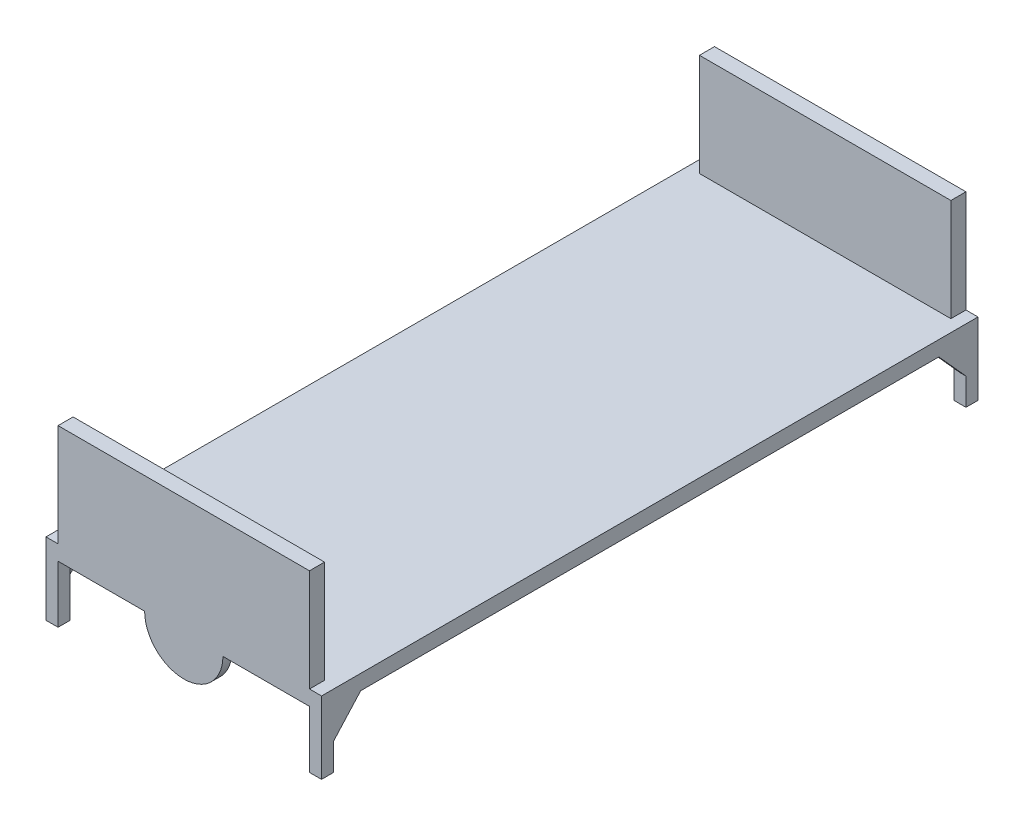
SolidWorks part; units mm, degrees
note: The reader was unsure of these and kept them because the rebuilt part matched: shared geometry of "Sketch1<3>", "Sketch1<4>".
ref_plane "Front Plane" through (0, 0, 0) normal (0, 0, 1) x (1, 0, 0)
ref_plane "Top Plane" through (0, 0, 0) normal (0, 1, 0) x (1, 0, 0)
ref_plane "Right Plane" through (0, 0, 0) normal (1, 0, 0) x (0, 0, -1)
sketch "Sketch1" plane through (0, 0, 0) normal (0, 1, 0) x (1, 0, 0)
  line L0 (-417.5, 40) -> (-457.5, 40)
  line L1 (457.5, 0) -> (-457.5, 0)
  line L2 (457.5, 0) -> (457.5, 2180)
  line L3 (457.5, 2180) -> (-457.5, 2180)
  line L4 (-457.5, 0) -> (-457.5, 2180)
  line L5 (-457.5, 0) -> (457.5, 0)
  line L6 (-457.5, 0) -> (-457.5, 50)
  line L7 (-457.5, 50) -> (457.5, 50)
  line L8 (457.5, 0) -> (457.5, 50)
  line L9 (-457.5, 2180) -> (457.5, 2180)
  line L10 (-457.5, 2180) -> (-457.5, 2130)
  line L11 (-457.5, 2130) -> (457.5, 2130)
  line L12 (457.5, 2180) -> (457.5, 2130)
  line L13 (457.5, 0) -> (417.5, 0)
  line L14 (457.5, 0) -> (457.5, 50)
  line L15 (457.5, 50) -> (417.5, 50)
  line L16 (417.5, 0) -> (417.5, 50)
  line L17 (-457.5, 0) -> (-417.5, 0)
  line L18 (-457.5, 0) -> (-457.5, 50)
  line L19 (-457.5, 50) -> (-417.5, 50)
  line L20 (-417.5, 0) -> (-417.5, 50)
  line L21 (-457.5, 2130) -> (-417.5, 2130)
  line L22 (-457.5, 2130) -> (-457.5, 2180)
  line L23 (-457.5, 2180) -> (-417.5, 2180)
  line L24 (-417.5, 2130) -> (-417.5, 2180)
  line L25 (457.5, 2180) -> (417.5, 2180)
  line L26 (457.5, 2180) -> (457.5, 2130)
  line L27 (457.5, 2130) -> (417.5, 2130)
  line L28 (417.5, 2180) -> (417.5, 2130)
  line L29 (457.5, 40) -> (417.5, 40)
  line L30 (-457.5, 2140) -> (-417.5, 2140)
  line L31 (417.5, 2140) -> (457.5, 2140)
  dimension "D1" = 2180
  dimension "D2" = 915
  dimension "D3" = 50
  dimension "D4" = 50
  dimension "D5" = 40
  dimension "D6" = 40
  dimension "D7" = 40
  dimension "D8" = 40
  dimension "D9" = 40
  dimension "D10" = 40
  dimension "D11" = 40
extrude "Boss-Extrude1" add sketch "Sketch1" against normal blind 50 contours L11 L4 L7 L2 | L0 L20 L7 L4 | L29 L14 L7 L16 | L31 L28 L11 L2 | L30 L4 L11 L24
extrude "Boss-Extrude2" add sketch "Sketch1<3>" against normal blind 50 and the other way blind 340 contours L20 L5 L16 L7 | L28 L9 L24 L11
sketch "Sketch1<3>" plane through (0, 0, 0) normal (0, 1, 0) x (1, 0, 0) same geometry as "Sketch1"
extrude "Boss-Extrude3" add sketch "Sketch1<4>" against normal blind 240 contours L28 L31 L26 L3 | L22 L30 L24 L9 | L1 L20 L0 L4 | L2 L29 L16 L1
sketch "Sketch1<4>" plane through (0, 0, 0) normal (0, 1, 0) x (1, 0, 0) same geometry as "Sketch1"
sketch "Sketch3" plane through (457.5, 0, 0) normal (1, 0, 0) x (0, 0, -1)
  line L0 (40, -150) -> (130, -50)
  line L1 (40, -240) -> (40, -50) construction
  line L2 (40, -50) -> (2140, -50) construction
  line L3 (2140, -150) -> (2050, -50)
  line L4 (2140, -240) -> (2140, -50) construction
  line M4 (40, -240) -> (40, -50)
  line M5 (40, -50) -> (2140, -50)
  line M6 (2140, -50) -> (2140, -240)
  dimension "D1" = 100
  dimension "D2" = 90
  dimension "D3" = 100
  dimension "D4" = 90
extrude "Boss-Extrude4" add sketch "Sketch3" against normal blind 20 contours L0 M4 M5 | L3 M6 M5
sketch "Sketch4" plane through (-457.5, 0, -45.75) normal (1, 0, 0) x (0, 0, -1)
  line L0 (-5.75, -150) -> (84.25, -50)
  line L1 (-5.75, -50) -> (2094.25, -50) construction
  line L2 (2094.25, -240) -> (2094.25, -50) construction
  line L3 (2094.25, -150) -> (2004.25, -50)
  line L4 (-5.75, -240) -> (-5.75, -50) construction
  line M18 (2094.25, -240) -> (2094.25, -50)
  line M19 (2094.25, -50) -> (-5.75, -50)
  line M20 (-5.75, -50) -> (-5.75, -240)
  dimension "D1" = 90
  dimension "D2" = 100
  dimension "D3" = 90
  dimension "D4" = 100
extrude "Boss-Extrude5" add sketch "Sketch4" along normal blind 20 contours L3 M18 M19 | L0 M20 M19
sketch "Sketch5" plane through (0, -240, 0) normal (0, -1, 0) x (1, 0, 0)
  line L0 (-437.5, -2180) -> (-437.5, 0)
  line L1 (-422.5, -2175) -> (-452.5, -2175)
  line L2 (-422.5, -2175) -> (-422.5, -2145)
  line L3 (-422.5, -2145) -> (-452.5, -2145)
  line L4 (-452.5, -2175) -> (-452.5, -2145)
  line L5 (422.5, -2175) -> (452.5, -2175)
  line L6 (422.5, -2175) -> (422.5, -2145)
  line L7 (422.5, -2145) -> (452.5, -2145)
  line L8 (452.5, -2175) -> (452.5, -2145)
  line L9 (422.5, -35) -> (452.5, -35)
  line L10 (422.5, -35) -> (422.5, -5)
  line L11 (422.5, -5) -> (452.5, -5)
  line L12 (452.5, -35) -> (452.5, -5)
  line L13 (-452.5, -35) -> (-422.5, -35)
  line L14 (-452.5, -35) -> (-452.5, -5)
  line L15 (-452.5, -5) -> (-422.5, -5)
  line L16 (-422.5, -35) -> (-422.5, -5)
  line L17 (-457.5, -2160) -> (457.5, -2160)
  line L22 (-457.5, -20) -> (457.5, -20)
  line L25 (437.5, 0) -> (437.5, -2180)
  line L26 (457.5, 0) -> (417.5, 0) construction
  line L27 (457.5, -2180) -> (417.5, -2180) construction
  line L31 (457.5, 0) -> (457.5, -40) construction
  line L32 (457.5, -2140) -> (457.5, -2180) construction
  line L33 (-457.5, -2140) -> (-457.5, -2180) construction
  line L34 (-417.5, -2180) -> (-457.5, -2180) construction
  line L35 (-417.5, 0) -> (-457.5, 0) construction
  line L36 (-457.5, 0) -> (-457.5, -40) construction
  point P16 (-452.5, -2160)
  point P29 (-437.5, -5)
  point P36 (-452.5, -20)
  point P43 (437.5, -2175)
  dimension "D1" = 30
extrude "Cut-Extrude1" cut sketch "Sketch5" against normal blind 200 contours L4 L3 L2 L1 | L6 L7 L8 L5 | L10 L11 L12 L9 | L14 L15 L16 L13
sketch "Sketch6" plane through (0, 0, 0) normal (0, 0, 1) x (1, 0, 0)
  line L0 (417.5, -50) -> (-417.5, -50) construction
  line L1 (130, -50) -> (-130, -50)
  arc A0 (-130, -50) -> (130, -50) centre (0, -50) ccw
  dimension "D1" = 130
extrude "Boss-Extrude6" add sketch "Sketch6" against normal blind 30
sketch "Sketch7" plane through (0, 0, -2180) normal (0, 0, -1) x (-1, 0, 0)
  line L0 (-417.5, -50) -> (417.5, -50) construction
  line L1 (130, -50) -> (-130, -50)
  arc A0 (130, -50) -> (-130, -50) centre (0, -50) cw
  dimension "D1" = 130
extrude "Boss-Extrude7" add sketch "Sketch7" against normal blind 30
sketch3d "3DSketch1"
  line L0 (0, -180, -30) -> (0, -140, -30)
  line L1 (0, -140, -30) -> (0, -140, -2150)
  line L2 (0, -140, -2150) -> (0, -180, -2150)
  line L3 (0, -180, -2150) -> (0, -180, -30)
  arc A0 (-130, -50, -30) -> (130, -50, -30) centre (0, -50, -30) ccw construction
  arc A1 (130, -50, -2150) -> (-130, -50, -2150) centre (0, -50, -2150) ccw construction
  point P6 (0, -50, 100)
  point P12 (0, -50, -2280)
  dimension "D1" = 40
extrude "Boss-Extrude8" add sketch "3DSketch1" along a picked direction on the side of the normal blind 20 and the other way blind 20 contours L1 L2 L3 L0
